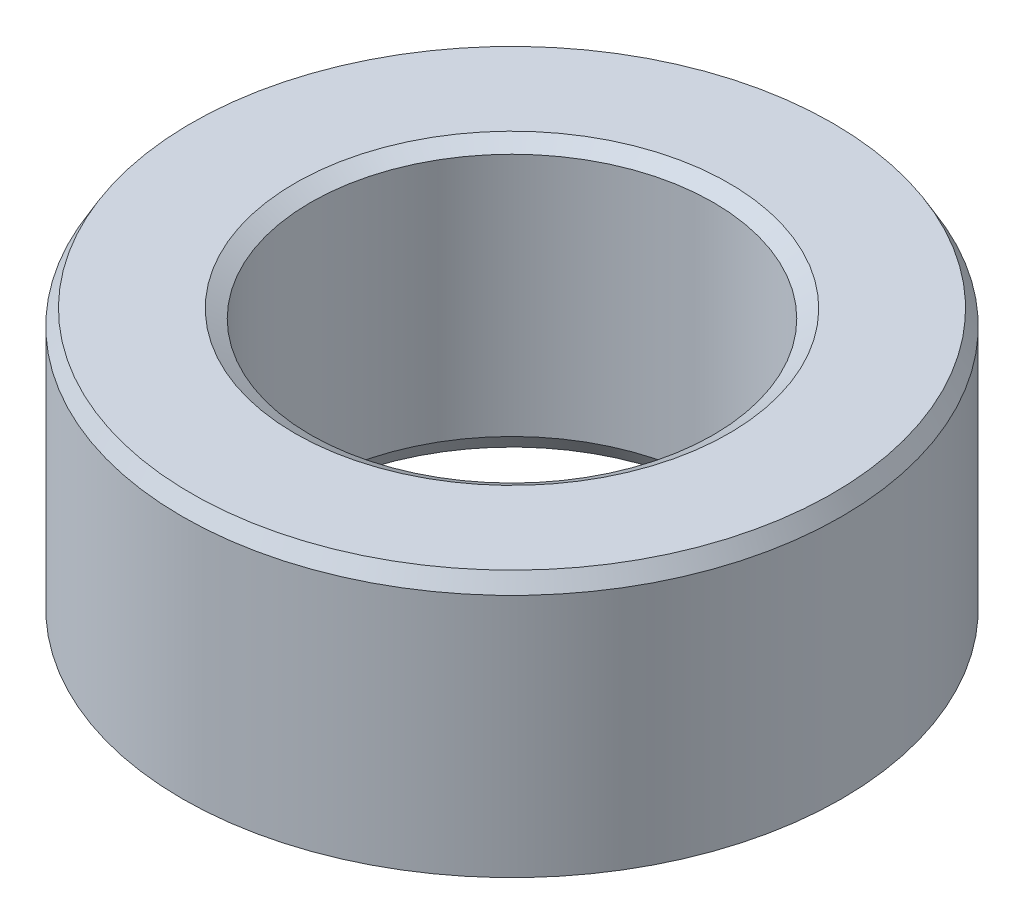
SolidWorks part; units mm, degrees
ref_plane "Front Plane" through (0, 0, 0) normal (0, 0, 1) x (1, 0, 0)
ref_plane "Top Plane" through (0, 0, 0) normal (0, 1, 0) x (1, 0, 0)
ref_plane "Right Plane" through (0, 0, 0) normal (1, 0, 0) x (0, 0, -1)
sketch "Sketch1" plane through (0, 0, 0) normal (0, 1, 0) x (1, 0, 0)
  circle A0 centre (0, 0) radius 57.5
  dimension "SLEEVE_OD" = 115
extrude "Boss-Extrude1" add sketch "Sketch1" along normal blind 46.9006
sketch "Sketch2" plane through (0, 0, 0) normal (0, 1, 0) x (1, 0, 0)
  circle A0 centre (0, 0) radius 35.1201
  dimension "BORE_D" = 70.2403
extrude "Cut-Extrude1" cut sketch "Sketch2" along normal through all
chamfer "Chamfer1" distance 2.7091 angle 30 4 edges at (0, 46.9006, 35.1201) (0, 0, 35.1201) (0, 0, 57.5) (0, 46.9006, 57.5) first distance on face at (0, 46.9006, 35.1201) first distance on face at (0, 0, 35.1201) first distance on face at (0, 46.9006, 57.5)
